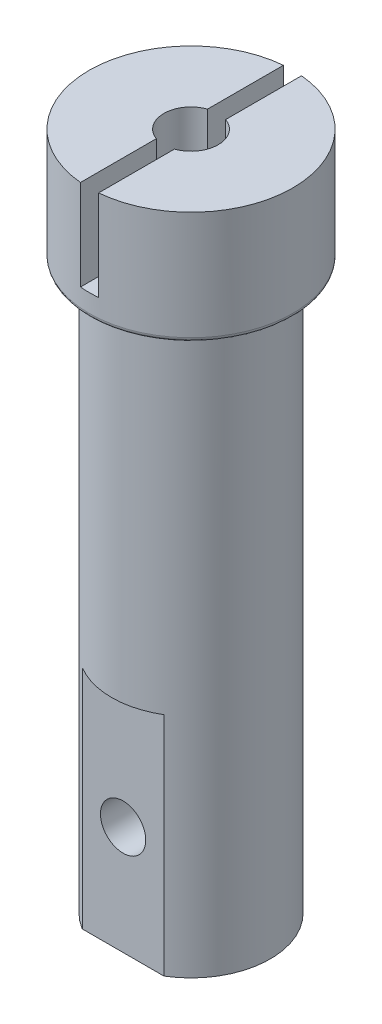
SolidWorks part; units mm, degrees
ref_plane "Front Plane" through (0, 0, 0) normal (0, 0, 1) x (1, 0, 0)
ref_plane "Top Plane" through (0, 0, 0) normal (0, 1, 0) x (1, 0, 0)
ref_plane "Right Plane" through (0, 0, 0) normal (1, 0, 0) x (0, 0, -1)
sketch "StockDiameter" plane through (0, 0, 0) normal (0, 1, 0) x (1, 0, 0)
  circle A0 centre (0, 0) radius 22.5
  dimension "D1" = 45
extrude "BaseStock" add sketch "StockDiameter" against normal blind 150
sketch "Sketch11" plane through (0, 0, 0) normal (0, 1, 0) x (1, 0, 0)
  circle A0 centre (0, 0) radius 17.5
  dimension "D1" = 35
extrude "DiameterCut" cut sketch "Sketch11" against normal through all from offset 25 flip side to cut offset against normal yes
sketch "ShaftHole" plane through (0, 0, 0) normal (0, 1, 0) x (1, 0, 0)
  circle A0 centre (0, 0) radius 6
  dimension "D1" = 12
extrude "Motor1ShaftHole" cut sketch "ShaftHole" against normal through all
sketch "Sketch10" plane through (0, 0, 0) normal (0, 0, 1) x (1, 0, 0)
  line L0 (22.5, 0) -> (-22.5, 0) construction
  line L1 (2, 0) -> (-2, 0)
  line L2 (2, 0) -> (2, -20)
  line L3 (2, -20) -> (-2, -20)
  line L4 (-2, 0) -> (-2, -20)
  line L5 (2, 0) -> (-2, -20) construction
  line L6 (2, -20) -> (-2, 0) construction
  point P0 (0, -10)
  point P8 (0, 0)
  dimension "D1" = 4
  dimension "D2" = 20
extrude "ShaftKey" cut sketch "Sketch10" against normal through all both and the other way through all contours L4 L3 L2 L1
sketch "ArmKeySketch" plane through (0, 0, 0) normal (0, 1, 0) x (1, 0, 0)
  line L1 (-30, -35) -> (30, -35)
  line L2 (-30, -35) -> (-30, -15)
  line L3 (-30, -15) -> (30, -15)
  line L4 (30, -35) -> (30, -15)
  point P4 (0, -15)
  dimension "D1" = 15
  dimension "D2" = 20
  dimension "D3" = 60
extrude "ArmKey" cut sketch "ArmKeySketch" along normal blind 50 from surface starting at face at (0, -150, 6)
sketch "Sketch13" plane through (0, 0, 0) normal (0, 0, 1) x (1, 0, 0)
  line L0 (9.0139, -150) -> (-9.0139, -150) construction
  circle A0 centre (0, -126) radius 5
  point P4 (0, 0)
  dimension "D2" = 10
  dimension "D1" = 24
extrude "Arm1MountingHole" cut sketch "Sketch13" against normal up to surface (11.6834 mm away) from surface up to face at (0, -150, 6) starting at face at (0, -125, 15)
fillet "Fillet1" radius 1 1 edges at (0, -25, 22.5)
equation "\"KeyDist\"= 15"
equation "\"D1@ArmKeySketch\"=\"KeyDist\""
equation "\"ArmWidth\"= 50"
equation "\"DrillHoleHeight\"= 24"
equation "\"D1@Sketch13\"=\"DrillHoleHeight\""
